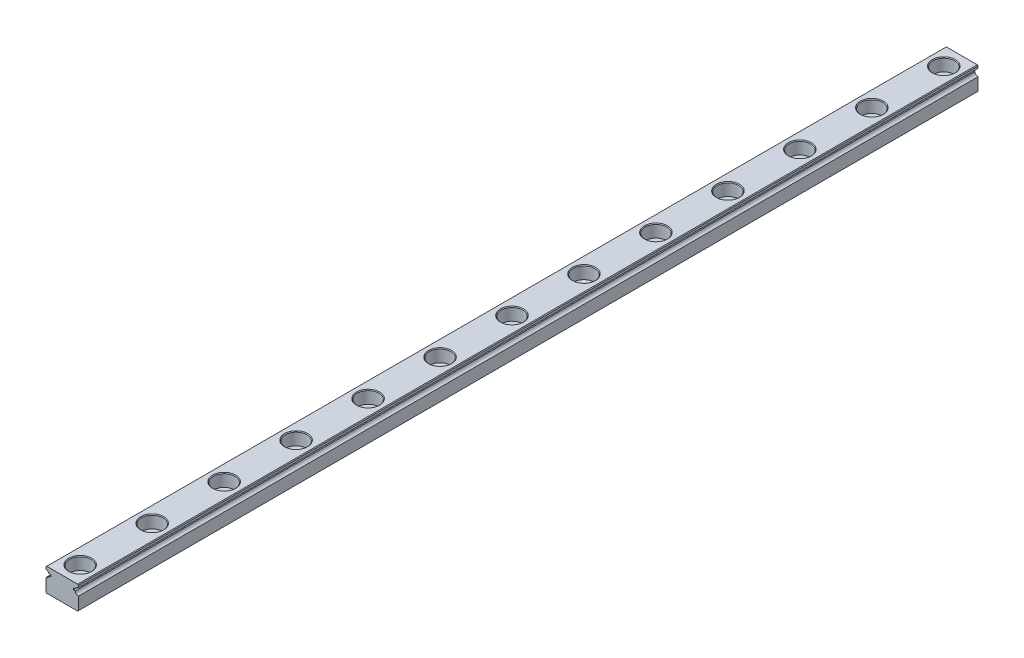
SolidWorks part; units mm, degrees
ref_plane "Спереди" through (0, 0, 0) normal (0, 0, 1) x (1, 0, 0)
ref_plane "Сверху" through (0, 0, 0) normal (0, 1, 0) x (1, 0, 0)
ref_plane "Справа" through (0, 0, 0) normal (1, 0, 0) x (0, 0, -1)
sketch "Sketch1" plane through (0, 0, 0) normal (0, 0, 1) x (1, 0, 0)
  line L0 (0, 0) -> (0, 4.3706) construction
  line L1 (-4.3, -3.25) -> (4.3, -3.25)
  line L2 (-4.5, -3.05) -> (-4.5, 0.455)
  line L3 (-4.3, 3.25) -> (4.3, 3.25)
  line L4 (4.5, -3.05) -> (4.5, 0.455)
  line L5 (-4.5, -3.25) -> (4.5, 3.25) construction
  line L6 (-4.5, 3.25) -> (4.5, -3.25) construction
  line L7 (-4.5, 2.445) -> (-4.5, 3.05)
  line L8 (4.5, 2.445) -> (4.5, 3.05)
  line L9 (-4.5, -3.05) -> (-4.3, -3.25)
  line L10 (4.3, -3.25) -> (4.5, -3.05)
  line L11 (4.3, 3.25) -> (4.5, 3.05)
  line L12 (-4.5, 3.05) -> (-4.3, 3.25)
  line L13 (3.6177, 1.2625) -> (3.1501, 1.2625)
  line L14 (-3.6177, 1.2625) -> (-3.1501, 1.2625)
  line L15 (3.1501, 1.2625) -> (3.1501, 1.7625)
  line L16 (-3.6501, 1.7625) -> (-3.1501, 1.7625)
  line L17 (-3.1501, 1.2625) -> (-3.1501, 1.7625)
  line L18 (3.6501, 1.7625) -> (3.1501, 1.7625)
  arc A0 (-4.5, 2.445) -> (-3.6501, 1.7625) centre (-4.6, 1.45) cw
  arc A1 (4.5, 2.445) -> (3.6501, 1.7625) centre (4.6, 1.45) ccw
  arc A2 (-3.6177, 1.2625) -> (-4.5, 0.455) centre (-4.6, 1.45) cw
  arc A3 (3.6177, 1.2625) -> (4.5, 0.455) centre (4.6, 1.45) ccw
  point P0 (0, 0)
  dimension "D4" = 1
  dimension "D5" = 0.1
  dimension "D1" = 9
  dimension "D2" = 6.5
  dimension "D3" = 1.8
  dimension "D6" = 0.5
  dimension "D7" = 0.5
extrude "Extrude1" add sketch "Sketch1" along normal blind 250
sketch "Sketch2" plane through (0, 3.25, 0) normal (0, 1, 0) x (1, 0, 0)
  line L0 (0, 0) -> (0, -5) construction
  circle A0 centre (0, -5) radius 1.75
  circle A1 centre (0, -5) radius 3
  dimension "D1" = 3.5
  dimension "D2" = 6
  dimension "D3" = 5
extrude "Extrude2" cut sketch "Sketch2" against normal up to next contours A0 region at (0, 3.25, 5)
extrude "Extrude4" cut sketch "Sketch" against normal blind 3.5
sketch "Sketch" plane through (0, 3.25, 0) normal (0, 1, 0) x (1, 0, 0) same geometry as "Sketch2"
chamfer "Chamfer1" distance 0.2 angle 45 2 edges at (0, -3.25, 6.75) (0, 3.25, 8)
pattern_linear "LPattern1" count 13 spacing 20 along (0, 0, 1) of "Extrude4", "Chamfer1", "Extrude2"
